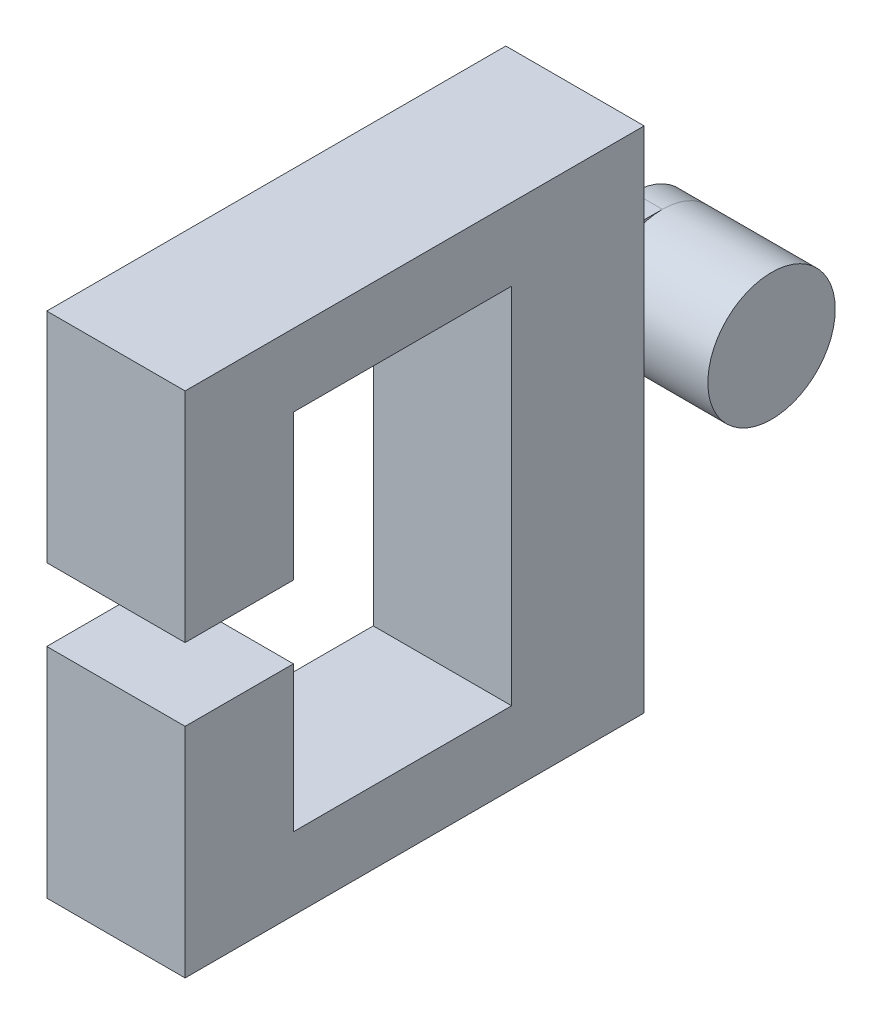
SolidWorks part; units mm, degrees
material "ASTM A36 Steel"
ref_plane "Front Plane" through (0, 0, 0) normal (1, 0, 0) x (0, 1, 0)
ref_plane "Top Plane" through (0, 0, 0) normal (0, 0, 1) x (0, 1, 0)
ref_plane "Right Plane" through (0, 0, 0) normal (0, 1, 0) x (-1, 0, 0)
sketch "Sketch1" plane through (0, 0, 0) normal (1, 0, 0) x (0, 1, 0)
  line L1 (-44.3535, 23.1252) -> (44.3535, 23.1252)
  line L2 (-44.3535, 23.1252) -> (-44.3535, 0)
  line L3 (-44.3535, 0) -> (44.3535, 0)
  line L4 (44.3535, 23.1252) -> (44.3535, 0)
  line L5 (-44.3535, 23.1252) -> (44.3535, 0) construction
  line L6 (-44.3535, 0) -> (44.3535, 23.1252) construction
  line L7 (-11.1128, 0) -> (11.1128, 0)
  line L8 (-11.1128, 0) -> (-11.1128, -33.3383)
  line L9 (-11.1128, -33.3383) -> (11.1128, -33.3383)
  line L10 (11.1128, 0) -> (11.1128, -33.3383)
  line L11 (-11.1128, 0) -> (11.1128, -33.3383) construction
  line L12 (-11.1128, -33.3383) -> (11.1128, 0) construction
  line L13 (-44.3535, 61.1998) -> (-31.7043, 61.1998)
  line L14 (-44.3535, 61.1998) -> (-44.3535, 23.1252)
  line L15 (-44.3535, 23.1252) -> (-31.7043, 23.1252)
  line L16 (-31.7043, 61.1998) -> (-31.7043, 23.1252)
  line L17 (-44.3535, 61.1998) -> (-31.7043, 23.1252) construction
  line L18 (-44.3535, 23.1252) -> (-31.7043, 61.1998) construction
  line L19 (31.7043, 61.1998) -> (44.3535, 61.1998)
  line L20 (31.7043, 61.1998) -> (31.7043, 23.1252)
  line L21 (31.7043, 23.1252) -> (44.3535, 23.1252)
  line L22 (44.3535, 61.1998) -> (44.3535, 23.1252)
  line L23 (31.7043, 61.1998) -> (44.3535, 23.1252) construction
  line L24 (31.7043, 23.1252) -> (44.3535, 61.1998) construction
  line L25 (-44.3535, 80.0915) -> (-6.3246, 80.0915)
  line L26 (-44.3535, 80.0915) -> (-44.3535, 61.1998)
  line L27 (-44.3535, 61.1998) -> (-6.3246, 61.1998)
  line L28 (-6.3246, 80.0915) -> (-6.3246, 61.1998)
  line L29 (-44.3535, 80.0915) -> (-6.3246, 61.1998) construction
  line L30 (-44.3535, 61.1998) -> (-6.3246, 80.0915) construction
  line L31 (6.3246, 80.0915) -> (44.3535, 80.0915)
  line L32 (6.3246, 80.0915) -> (6.3246, 61.1998)
  line L33 (6.3246, 61.1998) -> (44.3535, 61.1998)
  line L34 (44.3535, 80.0915) -> (44.3535, 61.1998)
  line L35 (6.3246, 80.0915) -> (44.3535, 61.1998) construction
  line L36 (6.3246, 61.1998) -> (44.3535, 80.0915) construction
  circle A0 centre (0, -22.2255) radius 11.1128
  point P0 (0, 11.5626)
  point P5 (0, -16.6691)
  point P13 (-25.339, 70.6457)
  point P15 (38.0289, 42.1625)
  point P16 (-38.0289, 42.1625)
  point P28 (0, 0)
  point P29 (25.339, 70.6457)
  dimension "D5" = 22.2255
  dimension "D6" = 12.6492
  dimension "D1" = 23.1252
  dimension "D2" = 88.707
  dimension "D3" = 22.2255
  dimension "D4" = 33.3383
  dimension "D7" = 38.0746
  dimension "D8" = 38.0289
  dimension "D9" = 18.8918
  dimension "D10" = 12.6492
  dimension "D11" = 25.3797
  dimension "D12" = 25.3797
extrude "Boss-Extrude1" add sketch "Sketch1" along normal mid plane 19.05 contours A0
sketch "Sketch2" plane through (-9.525, 0, 0) normal (-1, 0, 0) x (0, -1, 0)
  line L0 (11.1128, -33.3383) -> (-11.1128, -33.3383) construction
  line L1 (11.1128, 0) -> (11.1128, -33.3383) construction
  line L2 (-11.1128, 0) -> (-11.1128, -33.3383) construction
  line L3 (11.1128, -33.3383) -> (-11.1128, -33.3383)
  line L4 (11.1128, 0) -> (11.1128, -33.3383)
  line L5 (-11.1128, 0) -> (-11.1128, -33.3383)
  line L6 (-11.1128, 0) -> (11.1128, 0)
extrude "Boss-Extrude2" add sketch "Sketch2" along normal blind 5.0917 contours L5 L3 L4 L6
fillet "Fillet1" radius 11.1128 1 edges at (-12.0708, 11.1128, -33.3383) type face fillet first side face at (-11.5617, 0, -33.3383) second side face at (-11.5617, 11.1128, -17.7804)
fillet "Fillet2" radius 11.1128 1 edges at (-12.0708, -11.1128, -33.3383) type face fillet first side face at (-12.0708, -5.5564, -33.3383) second side face at (-11.5617, -11.1128, -17.7804)
extrude "Boss-Extrude3" add sketch "Sketch1<3>" along normal mid plane 19.05 separate body contours L4 L3 L2 L1 | L14 L13 L16 L15 | L26 L25 L28 L27 | L32 L31 L34 L33 | L20 L19 L22 L21
sketch "Sketch1<3>" plane through (0, 0, 0) normal (1, 0, 0) x (0, 1, 0) same geometry as "Sketch1"
sketch "Sketch8" plane through (-9.525, 0, 0) normal (-1, 0, 0) x (0, -1, 0)
  line L0 (31.7043, 61.1998) -> (31.7043, 23.1252) construction
  line L1 (31.7043, 23.1252) -> (-31.7043, 23.1252) construction
  line L2 (-31.7043, 61.1998) -> (-31.7043, 23.1252) construction
  line L3 (-6.3246, 61.1998) -> (-31.7043, 61.1998) construction
  line L4 (31.7043, 61.1998) -> (6.3246, 61.1998) construction
  line L5 (6.3246, 80.0915) -> (6.3246, 61.1998) construction
  line L6 (-6.3246, 80.0915) -> (-6.3246, 61.1998) construction
  line L7 (-6.3246, 80.0915) -> (-44.3535, 80.0915) construction
  line L8 (44.3535, 80.0915) -> (6.3246, 80.0915) construction
  line L9 (44.3535, 80.0915) -> (44.3535, 0) construction
  line L10 (44.3535, 0) -> (-44.3535, 0) construction
  line L11 (-44.3535, 80.0915) -> (-44.3535, 0) construction
  line L12 (31.7043, 61.1998) -> (31.7043, 23.1252)
  line L13 (31.7043, 23.1252) -> (-31.7043, 23.1252)
  line L14 (-31.7043, 61.1998) -> (-31.7043, 23.1252)
  line L15 (-6.3246, 61.1998) -> (-31.7043, 61.1998)
  line L16 (31.7043, 61.1998) -> (6.3246, 61.1998)
  line L17 (6.3246, 80.0915) -> (6.3246, 61.1998)
  line L18 (-6.3246, 80.0915) -> (-6.3246, 61.1998)
  line L19 (-6.3246, 80.0915) -> (-44.3535, 80.0915)
  line L20 (44.3535, 80.0915) -> (6.3246, 80.0915)
  line L21 (44.3535, 80.0915) -> (44.3535, 0)
  line L22 (44.3535, 0) -> (-44.3535, 0)
  line L23 (-44.3535, 80.0915) -> (-44.3535, 0)
extrude "Boss-Extrude6" add sketch "Sketch8" along normal blind 5.0917
